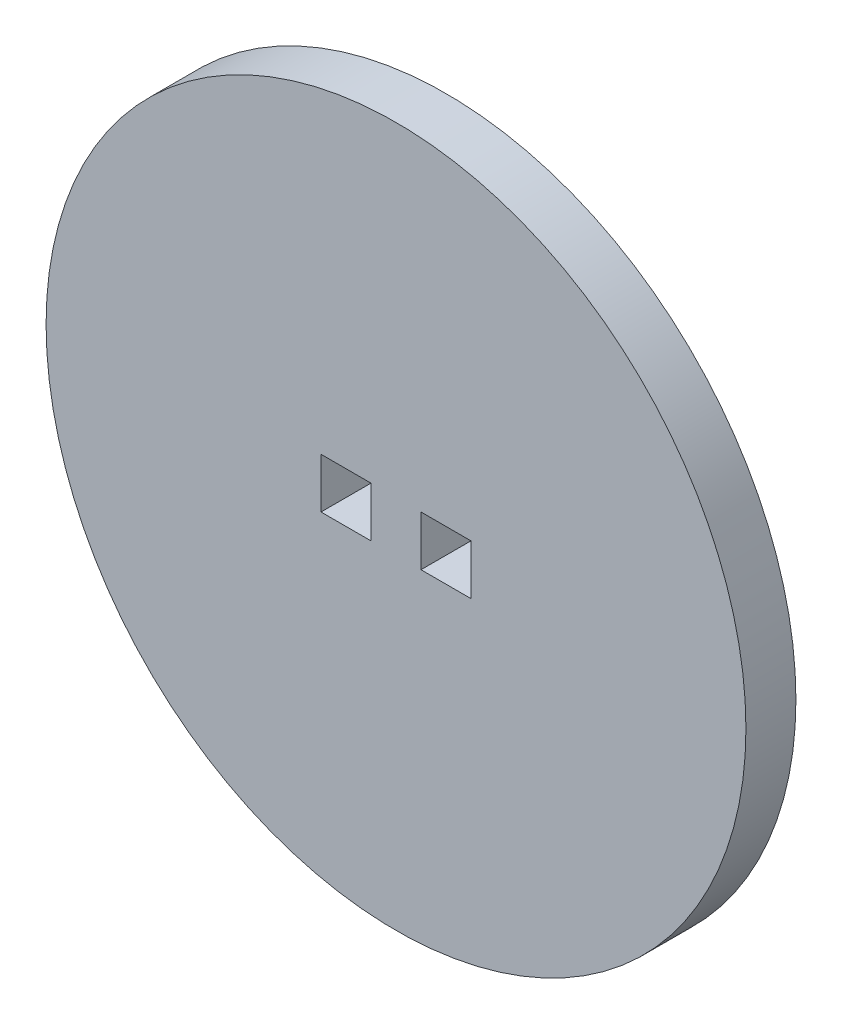
SolidWorks part; units mm, degrees
ref_plane "Front Plane" through (0, 0, 0) normal (0, 0, 1) x (1, 0, 0)
ref_plane "Top Plane" through (0, 0, 0) normal (0, 1, 0) x (1, 0, 0)
ref_plane "Right Plane" through (0, 0, 0) normal (1, 0, 0) x (0, 0, -1)
sketch "Sketch1" plane through (0, 0, 0) normal (0, 0, 1) x (1, 0, 0)
  line L0 (-1.5875, 0) -> (1.5875, 0) construction
  line L1 (1.5875, -1.5875) -> (4.7625, -1.5875)
  line L2 (1.5875, -1.5875) -> (1.5875, 1.5875)
  line L3 (1.5875, 1.5875) -> (4.7625, 1.5875)
  line L4 (4.7625, -1.5875) -> (4.7625, 1.5875)
  line L5 (-4.7625, 1.5875) -> (-1.5875, 1.5875)
  line L6 (-4.7625, 1.5875) -> (-4.7625, -1.5875)
  line L7 (-4.7625, -1.5875) -> (-1.5875, -1.5875)
  line L8 (-1.5875, 1.5875) -> (-1.5875, -1.5875)
  circle A0 centre (0, 0) radius 22.225
  point P13 (0, 0)
  dimension "D1" = 44.45
  dimension "D2" = 3.175
  dimension "D3" = 3.175
extrude "Boss-Extrude1" add sketch "Sketch1" along normal blind 3.175
equation "\"1.25i\"=4.63913"
